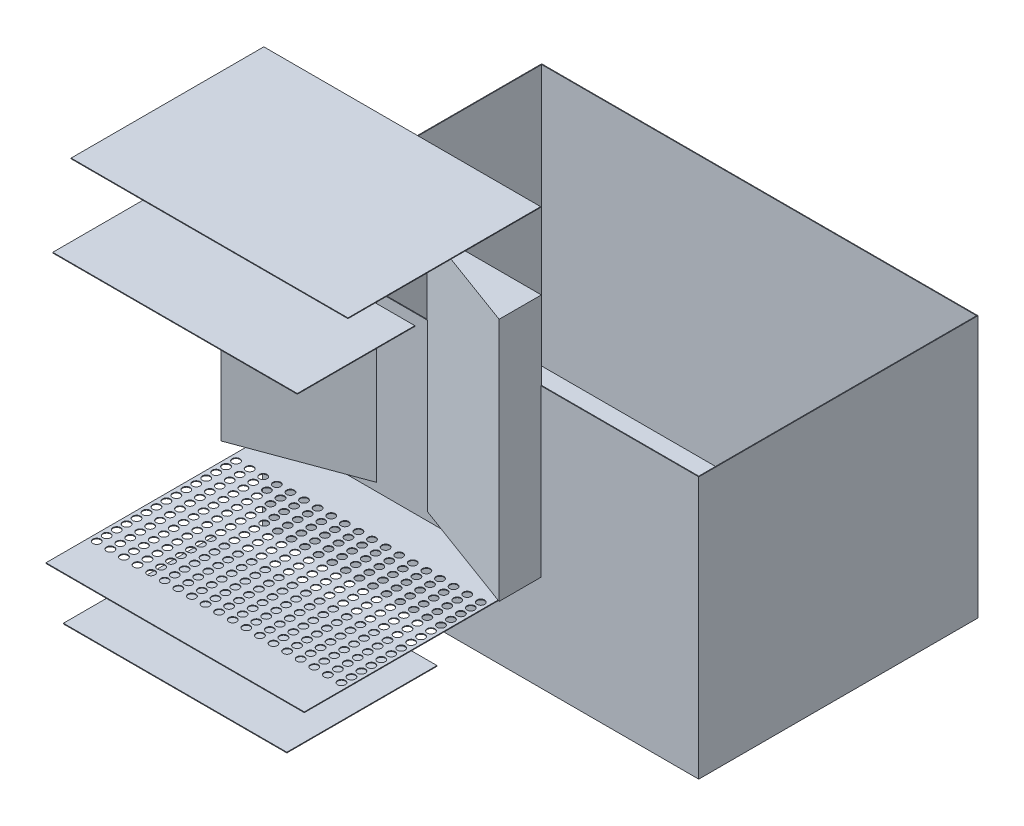
SolidWorks part; units mm, degrees
ref_plane "Спереди" through (0, 0, 0) normal (0, 0, 1) x (1, 0, 0)
ref_plane "Сверху" through (0, 0, 0) normal (0, 1, 0) x (1, 0, 0)
ref_plane "Справа" through (0, 0, 0) normal (1, 0, 0) x (0, 0, -1)
sketch "MASTER_FOOTPRINT" plane through (0, 0, 0) normal (0, 1, 0) x (1, 0, 0)
  line L1 (0, 0) -> (1250, 0)
  line L2 (0, 0) -> (0, 800)
  line L3 (0, 800) -> (1250, 800)
  line L4 (1250, 0) -> (1250, 800)
  dimension "D1" = 1250
  dimension "D2" = 800
extrude "BATH_BASE_PLATE" add sketch "MASTER_FOOTPRINT" along normal blind 750
shell "BATH_SHELL_2MM" thickness 2 removed face at (625, 750, -400)
sketch "Эскиз1" plane through (0, 0, 0) normal (0, 1, 0) x (1, 0, 0)
  line L1 (80, -220) -> (720, -220)
  line L2 (80, -220) -> (80, -650)
  line L3 (80, -650) -> (720, -650)
  line L4 (720, -220) -> (720, -650)
extrude "INLET_IMPACT_BAFFLE" add sketch "Эскиз1" along normal blind 2 from offset 125 separate body
sketch "Эскиз2" plane through (0, 0, 0) normal (0, 1, 0) x (1, 0, 0)
  line L0 (2, 2) -> (1248, 2) construction
  line L1 (30, 2) -> (770, 2)
  line L2 (30, 2) -> (30, -650)
  line L3 (30, -650) -> (770, -650)
  line L4 (770, 2) -> (770, -650)
  circle A0 centre (49.4737, -125) radius 11
  circle A1 centre (49.4737, -153.5) radius 11
  circle A2 centre (49.4737, -182) radius 11
  circle A3 centre (49.4737, -210.5) radius 11
  circle A4 centre (49.4737, -239) radius 11
  circle A5 centre (49.4737, -267.5) radius 11
  circle A6 centre (49.4737, -296) radius 11
  circle A7 centre (49.4737, -324.5) radius 11
  circle A8 centre (49.4737, -353) radius 11
  circle A9 centre (49.4737, -381.5) radius 11
  circle A10 centre (49.4737, -410) radius 11
  circle A11 centre (49.4737, -438.5) radius 11
  circle A12 centre (49.4737, -467) radius 11
  circle A13 centre (49.4737, -495.5) radius 11
  circle A14 centre (49.4737, -524) radius 11
  circle A15 centre (88.4211, -125) radius 11
  circle A16 centre (88.4211, -153.5) radius 11
  circle A17 centre (88.4211, -182) radius 11
  circle A18 centre (88.4211, -210.5) radius 11
  circle A19 centre (88.4211, -239) radius 11
  circle A20 centre (88.4211, -267.5) radius 11
  circle A21 centre (88.4211, -296) radius 11
  circle A22 centre (88.4211, -324.5) radius 11
  circle A23 centre (88.4211, -353) radius 11
  circle A24 centre (88.4211, -381.5) radius 11
  circle A25 centre (88.4211, -410) radius 11
  circle A26 centre (88.4211, -438.5) radius 11
  circle A27 centre (88.4211, -467) radius 11
  circle A28 centre (88.4211, -495.5) radius 11
  circle A29 centre (88.4211, -524) radius 11
  circle A30 centre (127.3684, -125) radius 11
  circle A31 centre (127.3684, -153.5) radius 11
  circle A32 centre (127.3684, -182) radius 11
  circle A33 centre (127.3684, -210.5) radius 11
  circle A34 centre (127.3684, -239) radius 11
  circle A35 centre (127.3684, -267.5) radius 11
  circle A36 centre (127.3684, -296) radius 11
  circle A37 centre (127.3684, -324.5) radius 11
  circle A38 centre (127.3684, -353) radius 11
  circle A39 centre (127.3684, -381.5) radius 11
  circle A40 centre (127.3684, -410) radius 11
  circle A41 centre (127.3684, -438.5) radius 11
  circle A42 centre (127.3684, -467) radius 11
  circle A43 centre (127.3684, -495.5) radius 11
  circle A44 centre (127.3684, -524) radius 11
  circle A45 centre (166.3158, -125) radius 11
  circle A46 centre (166.3158, -153.5) radius 11
  circle A47 centre (166.3158, -182) radius 11
  circle A48 centre (166.3158, -210.5) radius 11
  circle A49 centre (166.3158, -239) radius 11
  circle A50 centre (166.3158, -267.5) radius 11
  circle A51 centre (166.3158, -296) radius 11
  circle A52 centre (166.3158, -324.5) radius 11
  circle A53 centre (166.3158, -353) radius 11
  circle A54 centre (166.3158, -381.5) radius 11
  circle A55 centre (166.3158, -410) radius 11
  circle A56 centre (166.3158, -438.5) radius 11
  circle A57 centre (166.3158, -467) radius 11
  circle A58 centre (166.3158, -495.5) radius 11
  circle A59 centre (166.3158, -524) radius 11
  circle A60 centre (205.2632, -125) radius 11
  circle A61 centre (205.2632, -153.5) radius 11
  circle A62 centre (205.2632, -182) radius 11
  circle A63 centre (205.2632, -210.5) radius 11
  circle A64 centre (205.2632, -239) radius 11
  circle A65 centre (205.2632, -267.5) radius 11
  circle A66 centre (205.2632, -296) radius 11
  circle A67 centre (205.2632, -324.5) radius 11
  circle A68 centre (205.2632, -353) radius 11
  circle A69 centre (205.2632, -381.5) radius 11
  circle A70 centre (205.2632, -410) radius 11
  circle A71 centre (205.2632, -438.5) radius 11
  circle A72 centre (205.2632, -467) radius 11
  circle A73 centre (205.2632, -495.5) radius 11
  circle A74 centre (205.2632, -524) radius 11
  circle A75 centre (244.2105, -125) radius 11
  circle A76 centre (244.2105, -153.5) radius 11
  circle A77 centre (244.2105, -182) radius 11
  circle A78 centre (244.2105, -210.5) radius 11
  circle A79 centre (244.2105, -239) radius 11
  circle A80 centre (244.2105, -267.5) radius 11
  circle A81 centre (244.2105, -296) radius 11
  circle A82 centre (244.2105, -324.5) radius 11
  circle A83 centre (244.2105, -353) radius 11
  circle A84 centre (244.2105, -381.5) radius 11
  circle A85 centre (244.2105, -410) radius 11
  circle A86 centre (244.2105, -438.5) radius 11
  circle A87 centre (244.2105, -467) radius 11
  circle A88 centre (244.2105, -495.5) radius 11
  circle A89 centre (244.2105, -524) radius 11
  circle A90 centre (283.1579, -125) radius 11
  circle A91 centre (283.1579, -153.5) radius 11
  circle A92 centre (283.1579, -182) radius 11
  circle A93 centre (283.1579, -210.5) radius 11
  circle A94 centre (283.1579, -239) radius 11
  circle A95 centre (283.1579, -267.5) radius 11
  circle A96 centre (283.1579, -296) radius 11
  circle A97 centre (283.1579, -324.5) radius 11
  circle A98 centre (283.1579, -353) radius 11
  circle A99 centre (283.1579, -381.5) radius 11
  circle A100 centre (283.1579, -410) radius 11
  circle A101 centre (283.1579, -438.5) radius 11
  circle A102 centre (283.1579, -467) radius 11
  circle A103 centre (283.1579, -495.5) radius 11
  circle A104 centre (283.1579, -524) radius 11
  circle A105 centre (322.1053, -125) radius 11
  circle A106 centre (322.1053, -153.5) radius 11
  circle A107 centre (322.1053, -182) radius 11
  circle A108 centre (322.1053, -210.5) radius 11
  circle A109 centre (322.1053, -239) radius 11
  circle A110 centre (322.1053, -267.5) radius 11
  circle A111 centre (322.1053, -296) radius 11
  circle A112 centre (322.1053, -324.5) radius 11
  circle A113 centre (322.1053, -353) radius 11
  circle A114 centre (322.1053, -381.5) radius 11
  circle A115 centre (322.1053, -410) radius 11
  circle A116 centre (322.1053, -438.5) radius 11
  circle A117 centre (322.1053, -467) radius 11
  circle A118 centre (322.1053, -495.5) radius 11
  circle A119 centre (322.1053, -524) radius 11
  circle A120 centre (361.0526, -125) radius 11
  circle A121 centre (361.0526, -153.5) radius 11
  circle A122 centre (361.0526, -182) radius 11
  circle A123 centre (361.0526, -210.5) radius 11
  circle A124 centre (361.0526, -239) radius 11
  circle A125 centre (361.0526, -267.5) radius 11
  circle A126 centre (361.0526, -296) radius 11
  circle A127 centre (361.0526, -324.5) radius 11
  circle A128 centre (361.0526, -353) radius 11
  circle A129 centre (361.0526, -381.5) radius 11
  circle A130 centre (361.0526, -410) radius 11
  circle A131 centre (361.0526, -438.5) radius 11
  circle A132 centre (361.0526, -467) radius 11
  circle A133 centre (361.0526, -495.5) radius 11
  circle A134 centre (361.0526, -524) radius 11
  circle A135 centre (400, -125) radius 11
  circle A136 centre (400, -153.5) radius 11
  circle A137 centre (400, -182) radius 11
  circle A138 centre (400, -210.5) radius 11
  circle A139 centre (400, -239) radius 11
  circle A140 centre (400, -267.5) radius 11
  circle A141 centre (400, -296) radius 11
  circle A142 centre (400, -324.5) radius 11
  circle A143 centre (400, -353) radius 11
  circle A144 centre (400, -381.5) radius 11
  circle A145 centre (400, -410) radius 11
  circle A146 centre (400, -438.5) radius 11
  circle A147 centre (400, -467) radius 11
  circle A148 centre (400, -495.5) radius 11
  circle A149 centre (400, -524) radius 11
  circle A150 centre (438.9474, -125) radius 11
  circle A151 centre (438.9474, -153.5) radius 11
  circle A152 centre (438.9474, -182) radius 11
  circle A153 centre (438.9474, -210.5) radius 11
  circle A154 centre (438.9474, -239) radius 11
  circle A155 centre (438.9474, -267.5) radius 11
  circle A156 centre (438.9474, -296) radius 11
  circle A157 centre (438.9474, -324.5) radius 11
  circle A158 centre (438.9474, -353) radius 11
  circle A159 centre (438.9474, -381.5) radius 11
  circle A160 centre (438.9474, -410) radius 11
  circle A161 centre (438.9474, -438.5) radius 11
  circle A162 centre (438.9474, -467) radius 11
  circle A163 centre (438.9474, -495.5) radius 11
  circle A164 centre (438.9474, -524) radius 11
  circle A165 centre (477.8947, -125) radius 11
  circle A166 centre (477.8947, -153.5) radius 11
  circle A167 centre (477.8947, -182) radius 11
  circle A168 centre (477.8947, -210.5) radius 11
  circle A169 centre (477.8947, -239) radius 11
  circle A170 centre (477.8947, -267.5) radius 11
  circle A171 centre (477.8947, -296) radius 11
  circle A172 centre (477.8947, -324.5) radius 11
  circle A173 centre (477.8947, -353) radius 11
  circle A174 centre (477.8947, -381.5) radius 11
  circle A175 centre (477.8947, -410) radius 11
  circle A176 centre (477.8947, -438.5) radius 11
  circle A177 centre (477.8947, -467) radius 11
  circle A178 centre (477.8947, -495.5) radius 11
  circle A179 centre (477.8947, -524) radius 11
  circle A180 centre (516.8421, -125) radius 11
  circle A181 centre (516.8421, -153.5) radius 11
  circle A182 centre (516.8421, -182) radius 11
  circle A183 centre (516.8421, -210.5) radius 11
  circle A184 centre (516.8421, -239) radius 11
  circle A185 centre (516.8421, -267.5) radius 11
  circle A186 centre (516.8421, -296) radius 11
  circle A187 centre (516.8421, -324.5) radius 11
  circle A188 centre (516.8421, -353) radius 11
  circle A189 centre (516.8421, -381.5) radius 11
  circle A190 centre (516.8421, -410) radius 11
  circle A191 centre (516.8421, -438.5) radius 11
  circle A192 centre (516.8421, -467) radius 11
  circle A193 centre (516.8421, -495.5) radius 11
  circle A194 centre (516.8421, -524) radius 11
  circle A195 centre (555.7895, -125) radius 11
  circle A196 centre (555.7895, -153.5) radius 11
  circle A197 centre (555.7895, -182) radius 11
  circle A198 centre (555.7895, -210.5) radius 11
  circle A199 centre (555.7895, -239) radius 11
  circle A200 centre (555.7895, -267.5) radius 11
  circle A201 centre (555.7895, -296) radius 11
  circle A202 centre (555.7895, -324.5) radius 11
  circle A203 centre (555.7895, -353) radius 11
  circle A204 centre (555.7895, -381.5) radius 11
  circle A205 centre (555.7895, -410) radius 11
  circle A206 centre (555.7895, -438.5) radius 11
  circle A207 centre (555.7895, -467) radius 11
  circle A208 centre (555.7895, -495.5) radius 11
  circle A209 centre (555.7895, -524) radius 11
  circle A210 centre (594.7368, -125) radius 11
  circle A211 centre (594.7368, -153.5) radius 11
  circle A212 centre (594.7368, -182) radius 11
  circle A213 centre (594.7368, -210.5) radius 11
  circle A214 centre (594.7368, -239) radius 11
  circle A215 centre (594.7368, -267.5) radius 11
  circle A216 centre (594.7368, -296) radius 11
  circle A217 centre (594.7368, -324.5) radius 11
  circle A218 centre (594.7368, -353) radius 11
  circle A219 centre (594.7368, -381.5) radius 11
  circle A220 centre (594.7368, -410) radius 11
  circle A221 centre (594.7368, -438.5) radius 11
  circle A222 centre (594.7368, -467) radius 11
  circle A223 centre (594.7368, -495.5) radius 11
  circle A224 centre (594.7368, -524) radius 11
  circle A225 centre (633.6842, -125) radius 11
  circle A226 centre (633.6842, -153.5) radius 11
  circle A227 centre (633.6842, -182) radius 11
  circle A228 centre (633.6842, -210.5) radius 11
  circle A229 centre (633.6842, -239) radius 11
  circle A230 centre (633.6842, -267.5) radius 11
  circle A231 centre (633.6842, -296) radius 11
  circle A232 centre (633.6842, -324.5) radius 11
  circle A233 centre (633.6842, -353) radius 11
  circle A234 centre (633.6842, -381.5) radius 11
  circle A235 centre (633.6842, -410) radius 11
  circle A236 centre (633.6842, -438.5) radius 11
  circle A237 centre (633.6842, -467) radius 11
  circle A238 centre (633.6842, -495.5) radius 11
  circle A239 centre (633.6842, -524) radius 11
  circle A240 centre (672.6316, -125) radius 11
  circle A241 centre (672.6316, -153.5) radius 11
  circle A242 centre (672.6316, -182) radius 11
  circle A243 centre (672.6316, -210.5) radius 11
  circle A244 centre (672.6316, -239) radius 11
  circle A245 centre (672.6316, -267.5) radius 11
  circle A246 centre (672.6316, -296) radius 11
  circle A247 centre (672.6316, -324.5) radius 11
  circle A248 centre (672.6316, -353) radius 11
  circle A249 centre (672.6316, -381.5) radius 11
  circle A250 centre (672.6316, -410) radius 11
  circle A251 centre (672.6316, -438.5) radius 11
  circle A252 centre (672.6316, -467) radius 11
  circle A253 centre (672.6316, -495.5) radius 11
  circle A254 centre (672.6316, -524) radius 11
  circle A255 centre (711.5789, -125) radius 11
  circle A256 centre (711.5789, -153.5) radius 11
  circle A257 centre (711.5789, -182) radius 11
  circle A258 centre (711.5789, -210.5) radius 11
  circle A259 centre (711.5789, -239) radius 11
  circle A260 centre (711.5789, -267.5) radius 11
  circle A261 centre (711.5789, -296) radius 11
  circle A262 centre (711.5789, -324.5) radius 11
  circle A263 centre (711.5789, -353) radius 11
  circle A264 centre (711.5789, -381.5) radius 11
  circle A265 centre (711.5789, -410) radius 11
  circle A266 centre (711.5789, -438.5) radius 11
  circle A267 centre (711.5789, -467) radius 11
  circle A268 centre (711.5789, -495.5) radius 11
  circle A269 centre (711.5789, -524) radius 11
  circle A270 centre (750.5263, -125) radius 11
  circle A271 centre (750.5263, -153.5) radius 11
  circle A272 centre (750.5263, -182) radius 11
  circle A273 centre (750.5263, -210.5) radius 11
  circle A274 centre (750.5263, -239) radius 11
  circle A275 centre (750.5263, -267.5) radius 11
  circle A276 centre (750.5263, -296) radius 11
  circle A277 centre (750.5263, -324.5) radius 11
  circle A278 centre (750.5263, -353) radius 11
  circle A279 centre (750.5263, -381.5) radius 11
  circle A280 centre (750.5263, -410) radius 11
  circle A281 centre (750.5263, -438.5) radius 11
  circle A282 centre (750.5263, -467) radius 11
  circle A283 centre (750.5263, -495.5) radius 11
  circle A284 centre (750.5263, -524) radius 11
extrude "DISTRIBUTOR_D22" add sketch "Эскиз2" along normal blind 2 from offset 250 separate body
sketch "Эскиз3" plane through (0, 0, 0) normal (0, 1, 0) x (1, 0, 0)
  line L0 (30, -650) -> (770, -650) construction
  line L1 (49.4737, -313.5) -> (750, -313.5)
  line L2 (49.4737, -313.5) -> (49.4737, -650)
  line L3 (49.4737, -650) -> (750, -650)
  line L4 (750, -313.5) -> (750, -650)
  circle A0 centre (49.4737, -324.5) radius 11 construction
extrude "OUTLET_SUBMERGED_BAFFLE" add sketch "Эскиз3" along normal blind 2 from offset 1030 separate body
sketch "Эскиз4" plane through (0, 0, 0) normal (0, 1, 0) x (1, 0, 0)
  line L1 (2, 2) -> (795, 2)
  line L2 (2, 2) -> (2, -550)
  line L3 (2, -550) -> (795, -550)
  line L4 (795, 2) -> (795, -550)
extrude "OVERFLOW_WEIR_Z550" add sketch "Эскиз4" along normal blind 2 from offset 1190 separate body
sketch "Эскиз5" plane through (0, 0, 0) normal (0, 1, 0) x (1, 0, 0)
  line L0 (2, 1) -> (2, -120)
  line L1 (2, -120) -> (330, 1)
  line L2 (330, 1) -> (2, 1)
  line L3 (798, 1) -> (798, -120)
  line L4 (798, -120) -> (470, 1)
  line L5 (470, 1) -> (798, 1)
extrude "SLOPED_SEDIMENT_FLOOR" add sketch "Эскиз5" along normal blind 700 from offset 275
sketch3d "SCREW_AXIS_30DEG_REFERENCE"
  line L0 (400, 400, 70) -> (400, 1350, 618.4828)
equation "\"AI_Q_Peak\"= 0.006"
equation "\"AI_B_Bath\" = 800"
equation "\"AI_L_Settle\" = 800"
equation "\"AI_L_Inlet\"= 250"
equation "\"AI_L_Outlet\"= 200"
equation "\"AI_L_Bath\" = 1250"
equation "\"AI_H_Water\"= 550"
equation "\"AI_H_Freeboard\"= 200"
equation "\"AI_H_Bath\"= 750"
equation "\"AI_Shell_Thickness\"= 2"
equation "\"AI_Inlet_DN\"= 100"
equation "\"AI_Weir_Width\"= 600"
equation "\"AI_Inlet_Baffle_Offset\"= 125"
equation "\"AI_Distributor_Open_Area\"= 0.28"
equation "\"AI_Distributor_Hole_Dia\"= 22"
equation "\"AI_Distributor_Blind_Zone\"= 110"
equation "\"AI_Outlet_Baffle_Depth\"= 250"
equation "\"AI_Screw_Diameter\"= 100"
equation "\"AI_Screw_Pitch\"= 100"
equation "\"AI_Screw_Angle\"= 30"
equation "\"AI_Screw_Rpm\"= 15"
equation "\"AI_Screw_Clearance\"= 5"
equation "\"AI_Liner_Thickness\"= 5"
equation "\"AI_Discharge_Height\"= 650"
equation "\"AI_Frame_Height\"= 500"
equation "\"D1@MASTER_FOOTPRINT\" = \"AI_L_Bath\""
equation "\"D2@MASTER_FOOTPRINT\" = \"AI_B_Bath\""
equation "\"D1@BATH_BASE_PLATE\" = \"AI_H_Bath\""
